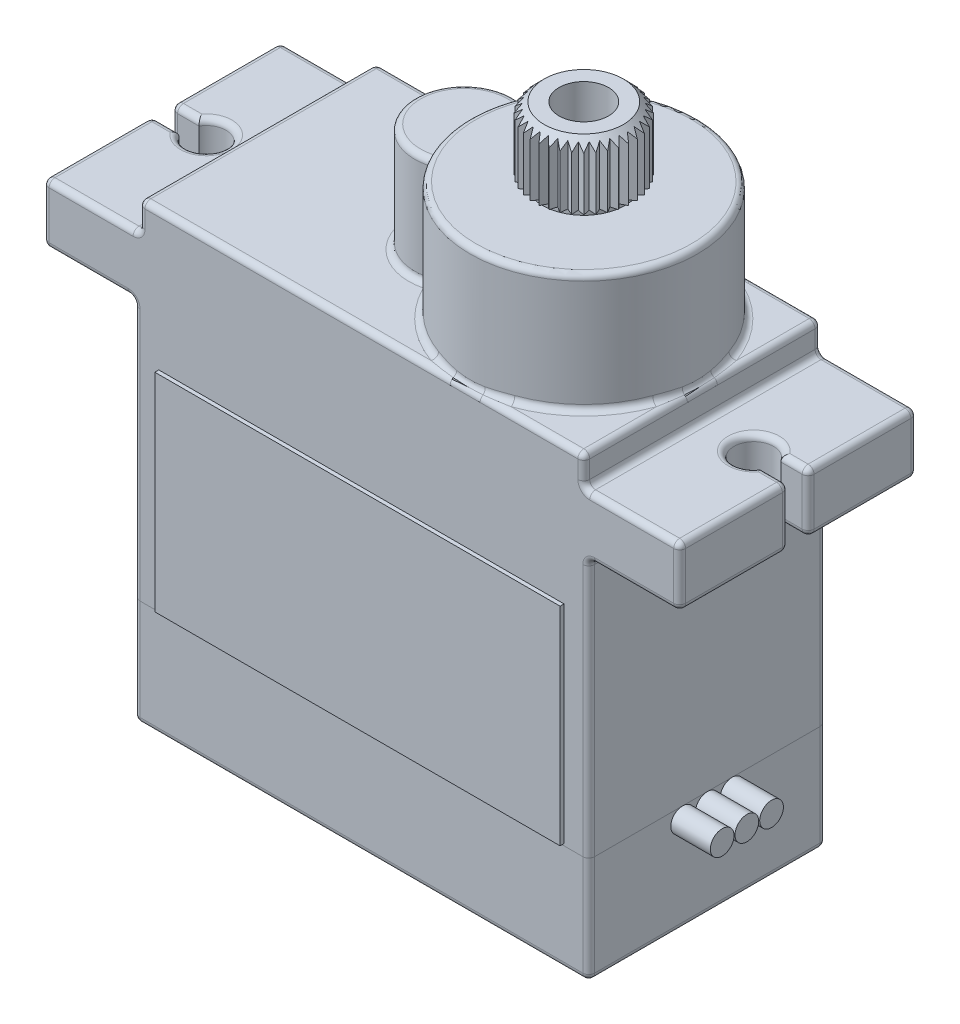
SolidWorks part; units mm, degrees
ref_plane "Front Plane" through (0, 0, 0) normal (0, 0, 1) x (1, 0, 0)
ref_plane "Top Plane" through (0, 0, 0) normal (0, 1, 0) x (1, 0, 0)
ref_plane "Right Plane" through (0, 0, 0) normal (1, 0, 0) x (0, 0, -1)
sketch "Sketch1" plane through (0, 0, 0) normal (0, 1, 0) x (1, 0, 0)
  line L1 (-11.5, -6) -> (11.5, -6)
  line L2 (-11.5, -6) -> (-11.5, 6)
  line L3 (-11.5, 6) -> (11.5, 6)
  line L4 (11.5, -6) -> (11.5, 6)
  line L5 (-11.5, -6) -> (11.5, 6) construction
  line L6 (-11.5, 6) -> (11.5, -6) construction
  point P0 (0, 0)
  dimension "D1" = 12
  dimension "D2" = 23
extrude "Boss-Extrude1" add sketch "Sketch1" along normal blind 18.5
sketch "Sketch2" plane through (0, 18.5, 0) normal (0, 1, 0) x (1, 0, 0)
  line L0 (11.5, 6) -> (-11.5, 6) construction
  line L1 (-16.1, -6) -> (16.1, -6)
  line L2 (-16.1, -6) -> (-16.1, 6)
  line L3 (-16.1, 6) -> (16.1, 6)
  line L4 (16.1, -6) -> (16.1, 6)
  line L5 (-16.1, -6) -> (16.1, 6) construction
  line L6 (-16.1, 6) -> (16.1, -6) construction
  point P0 (0, 0)
  dimension "D1" = 32.2
extrude "Boss-Extrude2" add sketch "Sketch2" along normal blind 3
sketch "Sketch3" plane through (0, 21.5, 0) normal (0, 1, 0) x (1, 0, 0)
  line L0 (16.1, 6) -> (-16.1, 6) construction
  line L1 (-11.25, -6) -> (11.25, -6)
  line L2 (-11.25, -6) -> (-11.25, 6)
  line L3 (-11.25, 6) -> (11.25, 6)
  line L4 (11.25, -6) -> (11.25, 6)
  line L5 (-11.25, -6) -> (11.25, 6) construction
  line L6 (-11.25, 6) -> (11.25, -6) construction
  point P0 (0, 0)
  dimension "D1" = 22.5
extrude "Boss-Extrude3" add sketch "Sketch3" along normal blind 1.5
sketch "Sketch4" plane through (0, 23, 0) normal (0, 1, 0) x (1, 0, 0)
  line L0 (-11.25, 6) -> (-11.25, -6) construction
  line L1 (5.25, 5.75) -> (5.25, 6) construction
  line L2 (11.25, 6) -> (-11.25, 6) construction
  line L3 (11, 0) -> (11.25, 0) construction
  line L4 (11.25, -6) -> (11.25, 6) construction
  line L5 (5.25, -5.75) -> (5.25, -6) construction
  line L6 (-11.25, -6) -> (11.25, -6) construction
  circle A0 centre (5.25, 0) radius 5.75
  point P5 (-11.25, 0)
  dimension "D1" = 11.5
extrude "Boss-Extrude4" add sketch "Sketch4" along normal blind 6
sketch "Sketch5" plane through (0, 23, 0) normal (0, 1, 0) x (1, 0, 0)
  line L0 (-11.25, 6) -> (-11.25, -6) construction
  circle A0 centre (-0.8, 0) radius 2.5
  circle A1 centre (5.25, 0) radius 5.75 construction
  circle A2 centre (5.25, 0) radius 5.75 construction
  point P2 (-3.3, 0)
  point P5 (-11.25, 0)
  point P6 (11, 0)
  dimension "D1" = 5
  dimension "D2" = 14.3
extrude "Boss-Extrude5" add sketch "Sketch5" along normal blind 5.5
sketch "Sketch6" plane through (0, 21.5, 0) normal (0, 1, 0) x (1, 0, 0)
  line L0 (-11.25, 6) -> (-11.25, -6) construction
  line L1 (0, 6) -> (0, -6) construction
  line L2 (11.25, 6) -> (-11.25, 6) construction
  line L3 (-11.25, -6) -> (11.25, -6) construction
  line L4 (-14.716, 0.5) -> (-16.1, 0.5)
  line L5 (-16.1, 6) -> (-16.1, -6) construction
  line L6 (-14.716, -0.5) -> (-16.1, -0.5)
  line L7 (-16.1, 0.5) -> (-16.1, -0.5)
  line L8 (16.1, 0.5) -> (16.1, -0.5)
  line L9 (14.716, -0.5) -> (16.1, -0.5)
  line L10 (14.716, 0.5) -> (16.1, 0.5)
  arc A0 (-14.716, -0.5) -> (-14.716, 0.5) centre (-13.85, 0) ccw
  arc A1 (14.716, -0.5) -> (14.716, 0.5) centre (13.85, 0) cw
  point P4 (-11.25, 0)
  dimension "D1" = 2
  dimension "D2" = 27.7
  dimension "D3" = 1
extrude "Cut-Extrude1" cut sketch "Sketch6" against normal through all
sketch "Sketch7" plane through (0, 29, 0) normal (0, 1, 0) x (1, 0, 0)
  circle A0 centre (5.25, 0) radius 2.5
  dimension "D1" = 5
extrude "Boss-Extrude6" add sketch "Sketch7" along normal blind 3.5
sketch "Sketch8" plane through (11.5, 0, 0) normal (1, 0, 0) x (0, 0, -1)
  line L0 (-1.25, 4.8) -> (1.25, 4.8) construction
  line L1 (-6, 0) -> (6, 0) construction
  circle A0 centre (-1.25, 4.8) radius 0.6
  circle A1 centre (0, 4.8) radius 0.6
  circle A2 centre (1.25, 4.8) radius 0.6
  dimension "D1" = 1.2
  dimension "D2" = 4.8
  dimension "D3" = 2.5
extrude "Boss-Extrude8" add sketch "Sketch8" along normal blind 2
fillet "Fillet1" radius 0.3 56 edges at (11.5, 0, 0) (11.5, 18.5, 0) (15.408, 18.5, 0.5) (12.85, 18.5, 0) (15.408, 18.5, -0.5) (15.408, 21.5, 0.5) (15.408, 21.5, -0.5) (12.85, 21.5, 0) (-11.25, 23, 0) (-15.408, 21.5, -0.5) (-11.25, 21.5, 0) (-15.408, 21.5, 0.5) (-12.85, 21.5, 0) (-16.1, 20, 0.5) (-16.1, 21.5, 3.25) (-16.1, 21.5, -3.25) (-16.1, 20, -0.5) (-16.1, 18.5, 3.25) (-16.1, 18.5, -3.25) (-15.408, 18.5, -0.5) (-12.85, 18.5, 0) (-15.408, 18.5, 0.5) (-11.5, 18.5, 0) (-11.5, 0, 0) (11.25, 23, 0) (11.25, 21.5, 0) (16.1, 21.5, 3.25) (16.1, 20, 0.5) (16.1, 18.5, 3.25) (16.1, 18.5, -3.25) (16.1, 20, -0.5) (16.1, 21.5, -3.25) (11.5, 9.25, -6) (13.8, 18.5, -6) (16.1, 20, -6) (13.675, 21.5, -6) (11.25, 22.25, -6) (0, 23, -6) (-11.25, 22.25, -6) (-13.675, 21.5, -6) (-16.1, 20, -6) (-13.8, 18.5, -6) (-11.5, 9.25, -6) (0, 0, -6) (-11.5, 9.25, 6) (-13.8, 18.5, 6) (-16.1, 20, 6) (-13.675, 21.5, 6) (-11.25, 22.25, 6) (0, 23, 6) (11.25, 22.25, 6) (13.675, 21.5, 6) (16.1, 20, 6) (13.8, 18.5, 6) (11.5, 9.25, 6) (0, 0, 6)
fillet "Fillet2" radius 0.3 10 edges at (5.25, 23, 5.75) (9.3159, 23, 4.0659) (11, 23, 0) (9.3159, 23, -4.0659) (5.25, 23, -5.75) (-3.3, 23, 0) (1.8189, 23, 4.6141) (1.8189, 23, -4.6141) (5.25, 29, 5.75) (-3.3, 28.5, 0)
chamfer "Chamfer1" distance 0.5 angle 45 1 edges at (5.25, 32.5, 2.5)
sketch "Sketch10" plane through (0, 32.5, 0) normal (0, 1, 0) x (1, 0, 0)
  line L0 (5.25, 0) -> (5.0321, 2.4905) construction
  line L1 (5.25, 0) -> (5.4679, 2.4905) construction
  line L2 (5.25, 0) -> (5.25, 2.5) construction
  line L3 (5.0321, 2.4905) -> (5.25, 2.2)
  line L4 (5.25, 2.2) -> (5.4679, 2.4905)
  line L5 (5.632, 2.1666) -> (5.897, 2.4148)
  line L6 (5.4679, 2.4905) -> (5.632, 2.1666)
  line L7 (6.0024, 2.0673) -> (6.3065, 2.2658)
  line L8 (5.897, 2.4148) -> (6.0024, 2.0673)
  line L9 (6.35, 1.9053) -> (6.6839, 2.0479)
  line L10 (6.3065, 2.2658) -> (6.35, 1.9053)
  line L11 (6.6641, 1.6853) -> (7.0178, 1.7678)
  line L12 (6.6839, 2.0479) -> (6.6641, 1.6853)
  line L13 (6.9353, 1.4141) -> (7.2979, 1.4339)
  line L14 (7.0178, 1.7678) -> (6.9353, 1.4141)
  line L15 (7.1553, 1.1) -> (7.5158, 1.0565)
  line L16 (7.2979, 1.4339) -> (7.1553, 1.1)
  line L17 (7.3173, 0.7524) -> (7.6648, 0.647)
  line L18 (7.5158, 1.0565) -> (7.3173, 0.7524)
  line L19 (7.4166, 0.382) -> (7.7405, 0.2179)
  line L20 (7.6648, 0.647) -> (7.4166, 0.382)
  line L21 (7.45, 0) -> (7.7405, -0.2179)
  line L22 (7.7405, 0.2179) -> (7.45, 0)
  line L23 (7.4166, -0.382) -> (7.6648, -0.647)
  line L24 (7.7405, -0.2179) -> (7.4166, -0.382)
  line L25 (7.3173, -0.7524) -> (7.5158, -1.0565)
  line L26 (7.6648, -0.647) -> (7.3173, -0.7524)
  line L27 (7.1553, -1.1) -> (7.2979, -1.4339)
  line L28 (7.5158, -1.0565) -> (7.1553, -1.1)
  line L29 (6.9353, -1.4141) -> (7.0178, -1.7678)
  line L30 (7.2979, -1.4339) -> (6.9353, -1.4141)
  line L31 (6.6641, -1.6853) -> (6.6839, -2.0479)
  line L32 (7.0178, -1.7678) -> (6.6641, -1.6853)
  line L33 (6.35, -1.9053) -> (6.3065, -2.2658)
  line L34 (6.6839, -2.0479) -> (6.35, -1.9053)
  line L35 (6.0024, -2.0673) -> (5.897, -2.4148)
  line L36 (6.3065, -2.2658) -> (6.0024, -2.0673)
  line L37 (5.632, -2.1666) -> (5.4679, -2.4905)
  line L38 (5.897, -2.4148) -> (5.632, -2.1666)
  line L39 (5.25, -2.2) -> (5.0321, -2.4905)
  line L40 (5.4679, -2.4905) -> (5.25, -2.2)
  line L41 (4.868, -2.1666) -> (4.603, -2.4148)
  line L42 (5.0321, -2.4905) -> (4.868, -2.1666)
  line L43 (4.4976, -2.0673) -> (4.1935, -2.2658)
  line L44 (4.603, -2.4148) -> (4.4976, -2.0673)
  line L45 (4.15, -1.9053) -> (3.8161, -2.0479)
  line L46 (4.1935, -2.2658) -> (4.15, -1.9053)
  line L47 (3.8359, -1.6853) -> (3.4822, -1.7678)
  line L48 (3.8161, -2.0479) -> (3.8359, -1.6853)
  line L49 (3.5647, -1.4141) -> (3.2021, -1.4339)
  line L50 (3.4822, -1.7678) -> (3.5647, -1.4141)
  line L51 (3.3447, -1.1) -> (2.9842, -1.0565)
  line L52 (3.2021, -1.4339) -> (3.3447, -1.1)
  line L53 (3.1827, -0.7524) -> (2.8352, -0.647)
  line L54 (2.9842, -1.0565) -> (3.1827, -0.7524)
  line L55 (3.0834, -0.382) -> (2.7595, -0.2179)
  line L56 (2.8352, -0.647) -> (3.0834, -0.382)
  line L57 (3.05, 0) -> (2.7595, 0.2179)
  line L58 (2.7595, -0.2179) -> (3.05, 0)
  line L59 (3.0834, 0.382) -> (2.8352, 0.647)
  line L60 (2.7595, 0.2179) -> (3.0834, 0.382)
  line L61 (3.1827, 0.7524) -> (2.9842, 1.0565)
  line L62 (2.8352, 0.647) -> (3.1827, 0.7524)
  line L63 (3.3447, 1.1) -> (3.2021, 1.4339)
  line L64 (2.9842, 1.0565) -> (3.3447, 1.1)
  line L65 (3.5647, 1.4141) -> (3.4822, 1.7678)
  line L66 (3.2021, 1.4339) -> (3.5647, 1.4141)
  line L67 (3.8359, 1.6853) -> (3.8161, 2.0479)
  line L68 (3.4822, 1.7678) -> (3.8359, 1.6853)
  line L69 (4.15, 1.9053) -> (4.1935, 2.2658)
  line L70 (3.8161, 2.0479) -> (4.15, 1.9053)
  line L71 (4.4976, 2.0673) -> (4.603, 2.4148)
  line L72 (4.1935, 2.2658) -> (4.4976, 2.0673)
  line L73 (4.868, 2.1666) -> (5.0321, 2.4905)
  line L74 (4.603, 2.4148) -> (4.868, 2.1666)
  circle A0 centre (5.25, 0) radius 2.5 construction
  arc A1 (5.4679, 2.4905) -> (5.0321, 2.4905) centre (5.25, 0) ccw
  circle A2 centre (5.25, 0) radius 2.2 construction
  arc A3 (5.897, 2.4148) -> (5.4679, 2.4905) centre (5.25, 0) ccw
  arc A4 (6.3065, 2.2658) -> (5.897, 2.4148) centre (5.25, 0) ccw
  arc A5 (6.6839, 2.0479) -> (6.3065, 2.2658) centre (5.25, 0) ccw
  arc A6 (7.0178, 1.7678) -> (6.6839, 2.0479) centre (5.25, 0) ccw
  arc A7 (7.2979, 1.4339) -> (7.0178, 1.7678) centre (5.25, 0) ccw
  arc A8 (7.5158, 1.0565) -> (7.2979, 1.4339) centre (5.25, 0) ccw
  arc A9 (7.6648, 0.647) -> (7.5158, 1.0565) centre (5.25, 0) ccw
  arc A10 (7.7405, 0.2179) -> (7.6648, 0.647) centre (5.25, 0) ccw
  arc A11 (7.7405, -0.2179) -> (7.7405, 0.2179) centre (5.25, 0) ccw
  arc A12 (7.6648, -0.647) -> (7.7405, -0.2179) centre (5.25, 0) ccw
  arc A13 (7.5158, -1.0565) -> (7.6648, -0.647) centre (5.25, 0) ccw
  arc A14 (7.2979, -1.4339) -> (7.5158, -1.0565) centre (5.25, 0) ccw
  arc A15 (7.0178, -1.7678) -> (7.2979, -1.4339) centre (5.25, 0) ccw
  arc A16 (6.6839, -2.0479) -> (7.0178, -1.7678) centre (5.25, 0) ccw
  arc A17 (6.3065, -2.2658) -> (6.6839, -2.0479) centre (5.25, 0) ccw
  arc A18 (5.897, -2.4148) -> (6.3065, -2.2658) centre (5.25, 0) ccw
  arc A19 (5.4679, -2.4905) -> (5.897, -2.4148) centre (5.25, 0) ccw
  arc A20 (5.0321, -2.4905) -> (5.4679, -2.4905) centre (5.25, 0) ccw
  arc A21 (4.603, -2.4148) -> (5.0321, -2.4905) centre (5.25, 0) ccw
  arc A22 (4.1935, -2.2658) -> (4.603, -2.4148) centre (5.25, 0) ccw
  arc A23 (3.8161, -2.0479) -> (4.1935, -2.2658) centre (5.25, 0) ccw
  arc A24 (3.4822, -1.7678) -> (3.8161, -2.0479) centre (5.25, 0) ccw
  arc A25 (3.2021, -1.4339) -> (3.4822, -1.7678) centre (5.25, 0) ccw
  arc A26 (2.9842, -1.0565) -> (3.2021, -1.4339) centre (5.25, 0) ccw
  arc A27 (2.8352, -0.647) -> (2.9842, -1.0565) centre (5.25, 0) ccw
  arc A28 (2.7595, -0.2179) -> (2.8352, -0.647) centre (5.25, 0) ccw
  arc A29 (2.7595, 0.2179) -> (2.7595, -0.2179) centre (5.25, 0) ccw
  arc A30 (2.8352, 0.647) -> (2.7595, 0.2179) centre (5.25, 0) ccw
  arc A31 (2.9842, 1.0565) -> (2.8352, 0.647) centre (5.25, 0) ccw
  arc A32 (3.2021, 1.4339) -> (2.9842, 1.0565) centre (5.25, 0) ccw
  arc A33 (3.4822, 1.7678) -> (3.2021, 1.4339) centre (5.25, 0) ccw
  arc A34 (3.8161, 2.0479) -> (3.4822, 1.7678) centre (5.25, 0) ccw
  arc A35 (4.1935, 2.2658) -> (3.8161, 2.0479) centre (5.25, 0) ccw
  arc A36 (4.603, 2.4148) -> (4.1935, 2.2658) centre (5.25, 0) ccw
  arc A37 (5.0321, 2.4905) -> (4.603, 2.4148) centre (5.25, 0) ccw
  point P114 (5.25, 0)
  dimension "D1" = 4.4
  dimension "D2" = 10
  dimension "D3" = 36
extrude "Cut-Extrude2" cut sketch "Sketch10" against normal up to surface (3.5 mm away) contours L69 A35 L70 | L67 A34 L68 | L65 A33 L66 | L63 A32 L64 | L61 A31 L62 | L59 A30 L60 | L57 A29 L58 | L55 A28 L56 | L53 A27 L54 | L51 A26 L52 | L49 A25 L50 | L45 A23 L46 | L43 A22 L44 | L41 A21 L42 | L39 A20 L40 | L37 A19 L38 | L35 A18 L36 | L33 A17 L34 | L31 A16 L32 | L29 A15 L30 | L27 A14 L28 | L25 A13 L26 | L23 A12 L24 | L21 A11 L22 | L19 A10 L20 | L17 A9 L18 | L15 A8 L16 | L13 A7 L14 | L11 A6 L12 | L9 A5 L10 | L7 A4 L8 | L5 A3 L6 | L4 A1 L3 | L73 A37 L74 | L71 A36 L72 | L47 A24 L48 region at (5.25, 32.5, -2.3979) region at (4.8336, 32.5, -2.3614) region at (5.6664, 32.5, -2.3614) region at (4.4299, 32.5, -2.2533) region at (6.0701, 32.5, -2.2533) region at (4.0511, 32.5, -2.0766) region at (6.4489, 32.5, -2.0766) region at (3.7087, 32.5, -1.8369) region at (6.7913, 32.5, -1.8369) region at (3.4131, 32.5, -1.5413) region at (7.0869, 32.5, -1.5413) region at (3.1734, 32.5, -1.1989) region at (7.3266, 32.5, -1.1989) region at (2.9967, 32.5, -0.8201) region at (7.5033, 32.5, -0.8201) region at (2.8886, 32.5, -0.4164) region at (7.6114, 32.5, -0.4164) region at (2.8521, 32.5, 0) region at (7.6479, 32.5, 0) region at (2.8886, 32.5, 0.4164) region at (7.6114, 32.5, 0.4164) region at (2.9967, 32.5, 0.8201) region at (7.5033, 32.5, 0.8201) region at (3.1734, 32.5, 1.1989) region at (7.3266, 32.5, 1.1989) region at (3.4131, 32.5, 1.5413) region at (7.0869, 32.5, 1.5413) region at (6.7913, 32.5, 1.8369) region at (4.0511, 32.5, 2.0766) region at (6.4489, 32.5, 2.0766) region at (4.4299, 32.5, 2.2533) region at (6.0701, 32.5, 2.2533) region at (4.8336, 32.5, 2.3614) region at (5.6664, 32.5, 2.3614) region at (5.25, 32.5, 2.3979) up to face at (5.25, 29, 5.45)
sketch "Sketch11" plane through (0, 0, 0) normal (0, 0, 1) x (1, 0, 0)
  line L0 (5.25, 32.5) -> (5.25, 27.5426) construction
  line L1 (7.9405, 29) -> (7.3405, 29)
  line L2 (7.9405, 29) -> (7.9405, 29.3)
  line L3 (7.9405, 29.3) -> (7.3405, 29.3)
  line L4 (7.3405, 29) -> (7.3405, 29.3)
  line L5 (7.25, 32.5) -> (3.25, 32.5) construction
  line L7 (10.7, 29) -> (-0.2, 29) construction
  line L8 (7.7405, 29) -> (7.7405, 32) construction
  dimension "D1" = 0.3
  dimension "D2" = 0.4
  dimension "D3" = 0.2
revolve "Cut-Revolve1" cut sketch "Sketch11" angle 360 about L0
sketch "Sketch12" plane through (0, 0, 6) normal (0, 0, 1) x (1, 0, 0)
  line L0 (11.2, 0) -> (-11.2, 0) construction
  line L1 (-10.25, 5.5) -> (10.25, 5.5)
  line L2 (-10.25, 5.5) -> (-10.25, 16)
  line L3 (-10.25, 16) -> (10.25, 16)
  line L4 (10.25, 5.5) -> (10.25, 16)
  line L5 (-10.25, 5.5) -> (10.25, 16) construction
  line L6 (-10.25, 16) -> (10.25, 5.5) construction
  point P0 (0, 10.75)
  dimension "D1" = 10.5
  dimension "D2" = 20.5
  dimension "D3" = 5.5
extrude "Boss-Extrude9" add sketch "Sketch12" along normal blind 0.2
sketch "Sketch13" plane through (0, 0, -6) normal (0, 0, -1) x (-1, 0, 0)
  line L4 (-10.25, 16) -> (-10.25, 5.5)
  line L5 (10.25, 16) -> (-10.25, 16)
  line L6 (10.25, 5.5) -> (10.25, 16)
  line L7 (-10.25, 5.5) -> (10.25, 5.5)
  line L8 (-10.25, 16) -> (-10.25, 5.5)
  line L9 (10.25, 16) -> (-10.25, 16)
  line L10 (10.25, 5.5) -> (10.25, 16)
  line L11 (-10.25, 5.5) -> (10.25, 5.5)
  dimension "D1" = 0
extrude "Boss-Extrude10" add sketch "Sketch13" along normal blind 0.2
ref_plane "Plane1" through (0, 5.4, 0) normal (0, 1, 0) x (1, 0, 0)
split line "Split Line1"
sketch "Sketch14" plane through (0, 32.5, 0) normal (0, 1, 0) x (1, 0, 0)
  circle A0 centre (5.25, 0) radius 1.25
  dimension "D1" = 2.5
extrude "Cut-Extrude3" cut sketch "Sketch14" against normal blind 2.5
